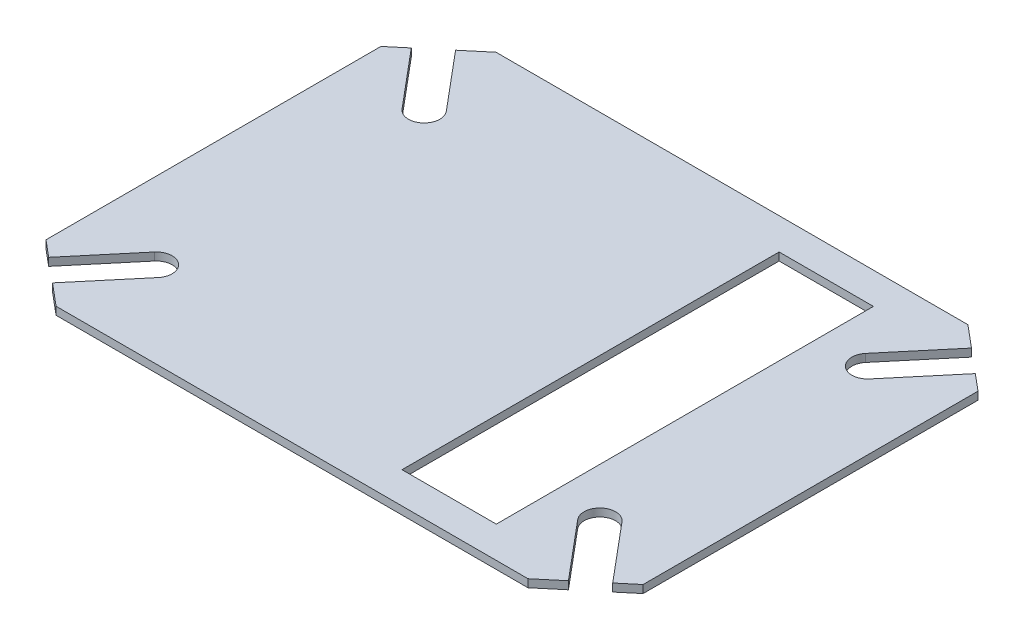
SolidWorks part; units mm, degrees
material "Thornel Mat VMA"
ref_plane "Front Plane" through (0, 0, 0) normal (0, 0, 1) x (1, 0, 0)
ref_plane "Top Plane" through (0, 0, 0) normal (0, 1, 0) x (1, 0, 0)
ref_plane "Right Plane" through (0, 0, 0) normal (1, 0, 0) x (0, 0, -1)
sketch "Sketch1" plane through (0, 0, 0) normal (0, 1, 0) x (1, 0, 0)
  line L0 (0, -95.25) -> (0, 95.25) construction
  line L1 (-127, 95.25) -> (127, 95.25) construction
  line L2 (-127, 95.25) -> (-127, -95.25) construction
  line L3 (-127, -95.25) -> (127, -95.25) construction
  line L4 (127, 95.25) -> (127, -95.25) construction
  line L5 (-127, 0) -> (127, 0) construction
  line L6 (-107.95, 0) -> (-107.95, 41.085) construction
  line L7 (-107.95, 41.085) -> (-95.25, 41.085) construction
  line L8 (-95.25, 41.085) -> (-75.7925, 57.4118) construction
  line L9 (-75.7925, 57.4118) -> (-75.7925, 76.2) construction
  line L10 (-75.7925, 76.2) -> (0, 76.2) construction
  line L11 (-127, 78.9232) -> (-107.5425, 95.25) construction
  line L12 (-75.7925, 57.4118) -> (-107.5425, 95.25) construction
  line L13 (-95.25, 41.085) -> (-127, 78.9232) construction
  line L14 (-120.65, 67.6728) -> (-113.9722, 73.2761)
  line L15 (-120.65, 88.9) -> (120.65, 88.9) construction
  line L16 (-120.65, 88.9) -> (-120.65, -88.9) construction
  line L17 (-120.65, -88.9) -> (120.65, -88.9) construction
  line L18 (120.65, 88.9) -> (120.65, -88.9) construction
  line L19 (-120.65, 88.9) -> (120.65, -88.9) construction
  line L20 (-120.65, -88.9) -> (120.65, 88.9) construction
  line L21 (120.65, 67.6728) -> (113.9722, 73.2761)
  line L22 (120.65, -67.6728) -> (113.9722, -73.2761)
  line L23 (-120.65, -67.6728) -> (-113.9722, -73.2761)
  line L24 (-95.3524, 88.9) -> (95.3524, 88.9)
  line L25 (-120.65, -67.6728) -> (-120.65, 67.6728)
  line L26 (120.65, 67.6728) -> (120.65, -67.6728)
  line L27 (95.3524, -88.9) -> (-95.3524, -88.9)
  line L28 (-85.5212, 49.2484) -> (-109.1078, 77.3578) construction
  line L29 (-109.1078, 77.3578) -> (-89.6029, 54.1128) construction
  line L30 (-104.2435, 81.4395) -> (-84.7386, 58.1945)
  line L31 (-113.9722, 73.2761) -> (-94.4673, 50.0311)
  line L32 (109.1078, 77.3578) -> (89.6029, 54.1128) construction
  line L33 (-104.2435, 81.4395) -> (-95.3524, 88.9)
  line L34 (104.2435, 81.4395) -> (84.7386, 58.1945)
  line L35 (113.9722, 73.2761) -> (94.4673, 50.0311)
  line L36 (104.2435, 81.4395) -> (95.3524, 88.9)
  line L37 (109.1078, -77.3578) -> (89.6029, -54.1128) construction
  line L38 (104.2435, -81.4395) -> (84.7386, -58.1945)
  line L39 (113.9722, -73.2761) -> (94.4673, -50.0311)
  line L40 (-109.1078, -77.3578) -> (-89.6029, -54.1128) construction
  line L41 (-104.2435, -81.4395) -> (-84.7386, -58.1945)
  line L42 (-113.9722, -73.2761) -> (-94.4673, -50.0311)
  line L43 (-104.2435, -81.4395) -> (-95.3524, -88.9)
  line L44 (104.2435, -81.4395) -> (95.3524, -88.9)
  arc A0 (-104.2435, 81.4395) -> (-113.9722, 73.2761) centre (-109.1078, 77.3578) ccw
  arc A1 (-94.4673, 50.0311) -> (-84.7386, 58.1945) centre (-89.6029, 54.1128) ccw
  arc A2 (104.2435, 81.4395) -> (113.9722, 73.2761) centre (109.1078, 77.3578) cw
  arc A3 (94.4673, 50.0311) -> (84.7386, 58.1945) centre (89.6029, 54.1128) cw
  arc A4 (104.2435, -81.4395) -> (113.9722, -73.2761) centre (109.1078, -77.3578) ccw
  arc A5 (94.4673, -50.0311) -> (84.7386, -58.1945) centre (89.6029, -54.1128) ccw
  arc A6 (-104.2435, -81.4395) -> (-113.9722, -73.2761) centre (-109.1078, -77.3578) cw
  arc A7 (-94.4673, -50.0311) -> (-84.7386, -58.1945) centre (-89.6029, -54.1128) cw
  point P8 (0, 0)
  point P18 (0, 0)
  point P33 (-99.3554, 65.7353)
  point P43 (99.3554, 65.7353)
  point P52 (99.3554, -65.7353)
  point P59 (-99.3554, -65.7353)
  dimension "D1" = 190.5
  dimension "D2" = 254
  dimension "D3" = 19.05
  dimension "D4" = 19.05
  dimension "D5" = 12.7
  dimension "D6" = 40
  dimension "D7" = 25.4
  dimension "D8" = 6.35
  dimension "D9" = 12.7
  dimension "D10" = 12.7
  dimension "D11" = 12.7
extrude "Boss-Extrude1" add sketch "Sketch1" along normal blind 3.175 contours L42 A7 L41 L43 L27 L44 L38 A5 L39 L22 L26 L21 L35 A3 L34 L36 L24 L33 L30 A1 L31 L14 L25 L23 region at (0, 0, 0)
sketch "Sketch2" plane through (0, 3.175, 0) normal (0, 1, 0) x (1, 0, 0)
  line L0 (0, 0) -> (120.65, 0) construction
  line L1 (120.65, 67.6728) -> (120.65, -67.6728) construction
  line L3 (31.75, 76.2) -> (69.85, 76.2)
  line L4 (31.75, 76.2) -> (31.75, -76.2)
  line L5 (31.75, -76.2) -> (69.85, -76.2)
  line L6 (69.85, 76.2) -> (69.85, -76.2)
  line L7 (31.75, 76.2) -> (69.85, -76.2) construction
  line L8 (31.75, -76.2) -> (69.85, 76.2) construction
  point P5 (50.8, 0)
  dimension "D1" = 38.1
  dimension "D2" = 152.4
  dimension "D3" = 50.8
extrude "Cut-Extrude1" cut sketch "Sketch2" against normal through all
